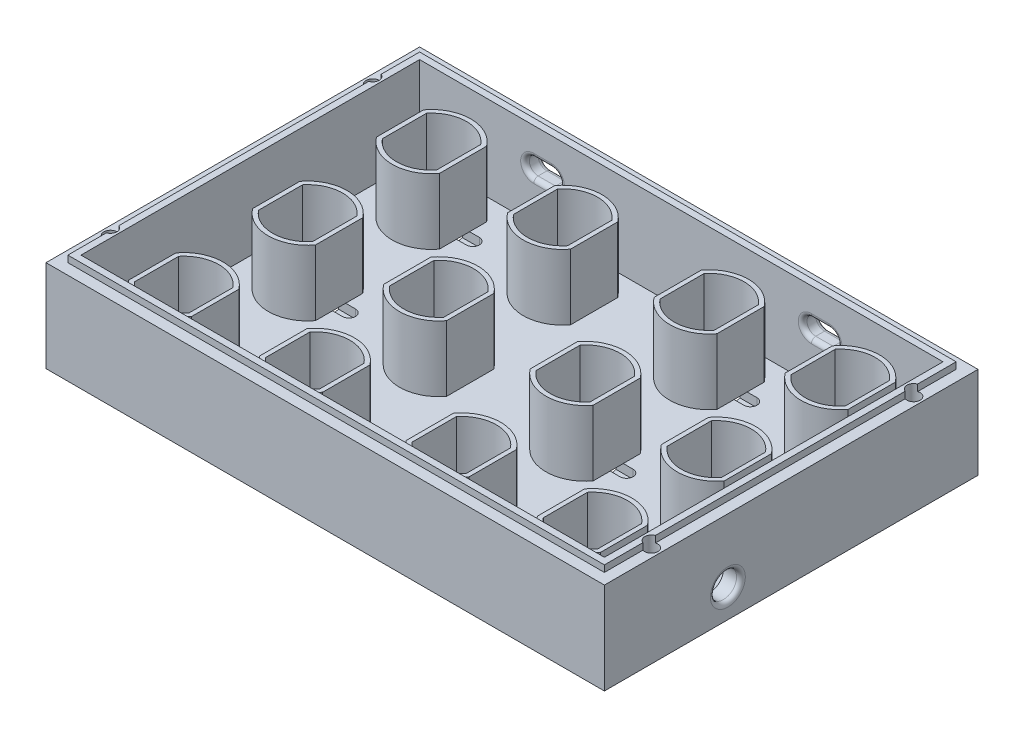
SolidWorks part; units mm, degrees
ref_plane "Front Plane" through (0, 0, 0) normal (0, 0, 1) x (1, 0, 0)
ref_plane "Top Plane" through (0, 0, 0) normal (0, 1, 0) x (1, 0, 0)
ref_plane "Right Plane" through (0, 0, 0) normal (1, 0, 0) x (0, 0, -1)
sketch "Sketch1" plane through (0, 0, 0) normal (0, 1, 0) x (1, 0, 0)
  line L0 (11.122, -9.411) -> (11.122, -19.379)
  line L1 (0, 0) -> (127.76, 0)
  line L2 (0, 0) -> (0, -85.48)
  line L3 (0, -85.48) -> (127.76, -85.48)
  line L4 (127.76, 0) -> (127.76, -85.48)
  line L5 (23.122, -9.411) -> (23.122, -19.379)
  line L6 (41.122, -9.411) -> (41.122, -19.379)
  line L7 (53.122, -9.411) -> (53.122, -19.379)
  line L8 (74.638, -9.411) -> (74.638, -19.379)
  line L9 (86.638, -9.411) -> (86.638, -19.379)
  line L10 (104.638, -9.411) -> (104.638, -19.379)
  line L11 (116.638, -9.411) -> (116.638, -19.379)
  line L12 (41.122, -37.756) -> (41.122, -47.724)
  line L13 (53.122, -37.756) -> (53.122, -47.724)
  line L14 (74.638, -37.756) -> (74.638, -47.724)
  line L15 (86.638, -37.756) -> (86.638, -47.724)
  line L16 (104.638, -37.756) -> (104.638, -47.724)
  line L17 (116.638, -37.756) -> (116.638, -47.724)
  line L18 (41.122, -66.101) -> (41.122, -76.069)
  line L19 (53.122, -66.101) -> (53.122, -76.069)
  line L20 (74.638, -66.101) -> (74.638, -76.069)
  line L21 (86.638, -66.101) -> (86.638, -76.069)
  line L22 (104.638, -66.101) -> (104.638, -76.069)
  line L23 (116.638, -66.101) -> (116.638, -76.069)
  line L24 (11.122, -37.756) -> (11.122, -47.724)
  line L25 (23.122, -37.756) -> (23.122, -47.724)
  line L26 (11.122, -66.101) -> (11.122, -76.069)
  line L27 (23.122, -66.101) -> (23.122, -76.069)
  circle A2 centre (17.122, -14.395) radius 14.05
  circle A12 centre (47.122, -14.395) radius 14.05
  circle A13 centre (80.638, -14.395) radius 14.05
  circle A14 centre (110.638, -14.395) radius 14.05
  circle A15 centre (47.122, -42.74) radius 14.05
  circle A16 centre (80.638, -42.74) radius 14.05
  circle A17 centre (110.638, -42.74) radius 14.05
  circle A18 centre (47.122, -71.085) radius 14.05
  circle A19 centre (80.638, -71.085) radius 14.05
  circle A20 centre (110.638, -71.085) radius 14.05
  circle A21 centre (17.122, -42.74) radius 14.05
  circle A22 centre (17.122, -71.085) radius 14.05
  arc A23 (11.122, -19.379) -> (23.122, -19.379) centre (17.122, -14.395) ccw
  arc A24 (23.122, -9.411) -> (11.122, -9.411) centre (17.122, -14.395) ccw
  arc A25 (41.122, -19.379) -> (53.122, -19.379) centre (47.122, -14.395) ccw
  arc A26 (53.122, -9.411) -> (41.122, -9.411) centre (47.122, -14.395) ccw
  arc A27 (74.638, -19.379) -> (86.638, -19.379) centre (80.638, -14.395) ccw
  arc A28 (86.638, -9.411) -> (74.638, -9.411) centre (80.638, -14.395) ccw
  arc A29 (104.638, -19.379) -> (116.638, -19.379) centre (110.638, -14.395) ccw
  arc A30 (116.638, -9.411) -> (104.638, -9.411) centre (110.638, -14.395) ccw
  arc A31 (41.122, -47.724) -> (53.122, -47.724) centre (47.122, -42.74) ccw
  arc A32 (53.122, -37.756) -> (41.122, -37.756) centre (47.122, -42.74) ccw
  arc A33 (74.638, -47.724) -> (86.638, -47.724) centre (80.638, -42.74) ccw
  arc A34 (86.638, -37.756) -> (74.638, -37.756) centre (80.638, -42.74) ccw
  arc A35 (104.638, -47.724) -> (116.638, -47.724) centre (110.638, -42.74) ccw
  arc A36 (116.638, -37.756) -> (104.638, -37.756) centre (110.638, -42.74) ccw
  arc A37 (41.122, -76.069) -> (53.122, -76.069) centre (47.122, -71.085) ccw
  arc A38 (53.122, -66.101) -> (41.122, -66.101) centre (47.122, -71.085) ccw
  arc A39 (74.638, -76.069) -> (86.638, -76.069) centre (80.638, -71.085) ccw
  arc A40 (86.638, -66.101) -> (74.638, -66.101) centre (80.638, -71.085) ccw
  arc A41 (104.638, -76.069) -> (116.638, -76.069) centre (110.638, -71.085) ccw
  arc A42 (116.638, -66.101) -> (104.638, -66.101) centre (110.638, -71.085) ccw
  arc A43 (11.122, -47.724) -> (23.122, -47.724) centre (17.122, -42.74) ccw
  arc A44 (23.122, -37.756) -> (11.122, -37.756) centre (17.122, -42.74) ccw
  arc A45 (11.122, -76.069) -> (23.122, -76.069) centre (17.122, -71.085) ccw
  arc A46 (23.122, -66.101) -> (11.122, -66.101) centre (17.122, -71.085) ccw
  point P15 (0, 0)
  point P17 (0, 0)
  point P34 (0, 0)
  point P35 (0, 0)
  point P44 (0, 0)
  point P49 (110.638, -42.9744)
  point P59 (82.4997, -14.7349)
  point P64 (110.638, -70.4806)
  point P69 (82.4997, -70.3296)
  point P74 (82.0649, -42.74)
  point P79 (17.122, -70.6281)
  point P89 (23.122, -19.379)
  point P91 (0, 0)
  point P92 (0, 0)
  point P93 (48.294, -44.3514)
  point P94 (0, 0)
  point P95 (0, 0)
  point P96 (46.1704, -70.4813)
  point P97 (0, 0)
  point P98 (110.638, -15.0922)
  point P99 (116.638, -19.379)
  point P100 (23.122, -76.069)
  point P101 (0, 0)
  point P102 (0, 0)
  point P103 (0, 0)
  point P104 (0, 0)
  point P105 (0, 0)
  point P106 (0, 0)
  point P107 (0, 0)
  dimension "D3" = 28.345
  dimension "D4" = 14.395
  dimension "D9" = 15.6
  dimension "D11" = 28.1
  dimension "D5" = 30
  dimension "D1" = 127.76
  dimension "D2" = 85.48
  dimension "D6" = 14.395
  dimension "D7" = 17.122
  dimension "D8" = 17.122
  dimension "D10" = 12
  dimension "D12" = 30
sketch "Sketch4" plane through (0, 0, 0) normal (0, 1, 0) x (1, 0, 0)
  line L44 (23.322, -19.4507) -> (23.322, -9.3393)
  line L45 (10.922, -9.3393) -> (10.922, -19.4507)
  line L46 (23.322, -19.4507) -> (23.322, -9.3393)
  line L47 (10.922, -9.3393) -> (10.922, -19.4507)
  line L50 (24.322, -19.795) -> (24.322, -8.995)
  line L51 (9.922, -8.995) -> (9.922, -19.795)
  line L52 (23.322, -47.7957) -> (23.322, -37.6843)
  line L53 (10.922, -37.6843) -> (10.922, -47.7957)
  line L54 (24.322, -48.14) -> (24.322, -37.34)
  line L55 (9.922, -37.34) -> (9.922, -48.14)
  line L56 (23.322, -76.1407) -> (23.322, -66.0293)
  line L57 (10.922, -66.0293) -> (10.922, -76.1407)
  line L58 (24.322, -76.485) -> (24.322, -65.685)
  line L59 (9.922, -65.685) -> (9.922, -76.485)
  line L60 (53.322, -19.4507) -> (53.322, -9.3393)
  line L61 (40.922, -9.3393) -> (40.922, -19.4507)
  line L62 (54.322, -19.795) -> (54.322, -8.995)
  line L63 (39.922, -8.995) -> (39.922, -19.795)
  line L64 (53.322, -47.7957) -> (53.322, -37.6843)
  line L65 (40.922, -37.6843) -> (40.922, -47.7957)
  line L66 (54.322, -48.14) -> (54.322, -37.34)
  line L67 (39.922, -37.34) -> (39.922, -48.14)
  line L68 (53.322, -76.1407) -> (53.322, -66.0293)
  line L69 (40.922, -66.0293) -> (40.922, -76.1407)
  line L70 (54.322, -76.485) -> (54.322, -65.685)
  line L71 (39.922, -65.685) -> (39.922, -76.485)
  line L72 (86.838, -19.4507) -> (86.838, -9.3393)
  line L73 (74.438, -9.3393) -> (74.438, -19.4507)
  line L74 (87.838, -19.795) -> (87.838, -8.995)
  line L75 (73.438, -8.995) -> (73.438, -19.795)
  line L76 (86.838, -47.7957) -> (86.838, -37.6843)
  line L77 (74.438, -37.6843) -> (74.438, -47.7957)
  line L78 (87.838, -48.14) -> (87.838, -37.34)
  line L79 (73.438, -37.34) -> (73.438, -48.14)
  line L80 (86.838, -76.1407) -> (86.838, -66.0293)
  line L81 (74.438, -66.0293) -> (74.438, -76.1407)
  line L82 (87.838, -76.485) -> (87.838, -65.685)
  line L83 (73.438, -65.685) -> (73.438, -76.485)
  line L84 (116.838, -19.4507) -> (116.838, -9.3393)
  line L85 (104.438, -9.3393) -> (104.438, -19.4507)
  line L86 (117.838, -19.795) -> (117.838, -8.995)
  line L87 (103.438, -8.995) -> (103.438, -19.795)
  line L88 (116.838, -47.7957) -> (116.838, -37.6843)
  line L89 (104.438, -37.6843) -> (104.438, -47.7957)
  line L90 (117.838, -48.14) -> (117.838, -37.34)
  line L91 (103.438, -37.34) -> (103.438, -48.14)
  line L92 (116.838, -76.1407) -> (116.838, -66.0293)
  line L93 (104.438, -66.0293) -> (104.438, -76.1407)
  line L94 (117.838, -76.485) -> (117.838, -65.685)
  line L95 (103.438, -65.685) -> (103.438, -76.485)
  arc A71 (24.322, -8.995) -> (9.922, -8.995) centre (17.122, -14.395) ccw
  arc A72 (9.922, -19.795) -> (24.322, -19.795) centre (17.122, -14.395) ccw
  arc A73 (24.322, -37.34) -> (9.922, -37.34) centre (17.122, -42.74) ccw
  arc A74 (9.922, -48.14) -> (24.322, -48.14) centre (17.122, -42.74) ccw
  arc A75 (10.922, -47.7957) -> (23.322, -47.7957) centre (17.122, -42.74) ccw
  arc A76 (23.322, -37.6843) -> (10.922, -37.6843) centre (17.122, -42.74) ccw
  arc A77 (24.322, -65.685) -> (9.922, -65.685) centre (17.122, -71.085) ccw
  arc A78 (9.922, -76.485) -> (24.322, -76.485) centre (17.122, -71.085) ccw
  arc A79 (10.922, -76.1407) -> (23.322, -76.1407) centre (17.122, -71.085) ccw
  arc A80 (23.322, -66.0293) -> (10.922, -66.0293) centre (17.122, -71.085) ccw
  arc A81 (54.322, -8.995) -> (39.922, -8.995) centre (47.122, -14.395) ccw
  arc A82 (39.922, -19.795) -> (54.322, -19.795) centre (47.122, -14.395) ccw
  arc A83 (54.322, -37.34) -> (39.922, -37.34) centre (47.122, -42.74) ccw
  arc A84 (39.922, -48.14) -> (54.322, -48.14) centre (47.122, -42.74) ccw
  arc A85 (40.922, -47.7957) -> (53.322, -47.7957) centre (47.122, -42.74) ccw
  arc A86 (53.322, -37.6843) -> (40.922, -37.6843) centre (47.122, -42.74) ccw
  arc A87 (54.322, -65.685) -> (39.922, -65.685) centre (47.122, -71.085) ccw
  arc A88 (39.922, -76.485) -> (54.322, -76.485) centre (47.122, -71.085) ccw
  arc A89 (40.922, -76.1407) -> (53.322, -76.1407) centre (47.122, -71.085) ccw
  arc A90 (53.322, -66.0293) -> (40.922, -66.0293) centre (47.122, -71.085) ccw
  arc A91 (40.922, -19.4507) -> (53.322, -19.4507) centre (47.122, -14.395) ccw
  arc A92 (53.322, -9.3393) -> (40.922, -9.3393) centre (47.122, -14.395) ccw
  arc A93 (87.838, -8.995) -> (73.438, -8.995) centre (80.638, -14.395) ccw
  arc A94 (73.438, -19.795) -> (87.838, -19.795) centre (80.638, -14.395) ccw
  arc A95 (87.838, -37.34) -> (73.438, -37.34) centre (80.638, -42.74) ccw
  arc A96 (73.438, -48.14) -> (87.838, -48.14) centre (80.638, -42.74) ccw
  arc A97 (74.438, -47.7957) -> (86.838, -47.7957) centre (80.638, -42.74) ccw
  arc A98 (86.838, -37.6843) -> (74.438, -37.6843) centre (80.638, -42.74) ccw
  arc A99 (87.838, -65.685) -> (73.438, -65.685) centre (80.638, -71.085) ccw
  arc A100 (73.438, -76.485) -> (87.838, -76.485) centre (80.638, -71.085) ccw
  arc A101 (74.438, -76.1407) -> (86.838, -76.1407) centre (80.638, -71.085) ccw
  arc A102 (86.838, -66.0293) -> (74.438, -66.0293) centre (80.638, -71.085) ccw
  arc A103 (117.838, -8.995) -> (103.438, -8.995) centre (110.638, -14.395) ccw
  arc A104 (103.438, -19.795) -> (117.838, -19.795) centre (110.638, -14.395) ccw
  arc A105 (117.838, -37.34) -> (103.438, -37.34) centre (110.638, -42.74) ccw
  arc A106 (103.438, -48.14) -> (117.838, -48.14) centre (110.638, -42.74) ccw
  arc A107 (104.438, -47.7957) -> (116.838, -47.7957) centre (110.638, -42.74) ccw
  arc A108 (116.838, -37.6843) -> (104.438, -37.6843) centre (110.638, -42.74) ccw
  arc A109 (117.838, -65.685) -> (103.438, -65.685) centre (110.638, -71.085) ccw
  arc A110 (103.438, -76.485) -> (117.838, -76.485) centre (110.638, -71.085) ccw
  arc A111 (104.438, -76.1407) -> (116.838, -76.1407) centre (110.638, -71.085) ccw
  arc A112 (10.922, -19.4507) -> (23.322, -19.4507) centre (17.122, -14.395) ccw
  arc A113 (23.322, -9.3393) -> (10.922, -9.3393) centre (17.122, -14.395) ccw
  arc A114 (10.922, -19.4507) -> (23.322, -19.4507) centre (17.122, -14.395) ccw
  arc A115 (23.322, -9.3393) -> (10.922, -9.3393) centre (17.122, -14.395) ccw
  arc A116 (116.838, -66.0293) -> (104.438, -66.0293) centre (110.638, -71.085) ccw
  arc A117 (104.438, -19.4507) -> (116.838, -19.4507) centre (110.638, -14.395) ccw
  arc A118 (116.838, -9.3393) -> (104.438, -9.3393) centre (110.638, -14.395) ccw
  arc A119 (74.438, -19.4507) -> (86.838, -19.4507) centre (80.638, -14.395) ccw
  arc A120 (86.838, -9.3393) -> (74.438, -9.3393) centre (80.638, -14.395) ccw
  point P10 (0, 0)
  dimension "D3" = 2
  dimension "D4" = 3
  dimension "D1" = 0.2
  dimension "D2" = 1
  dimension "D5" = 2
extrude "Boss-Extrude1" add sketch "Sketch4" along normal blind 15 contours L62 A81 L63 A82 | L60 A92 L61 A91 | L50 A71 L51 A72 | L46 A115 L47 A114 | L54 A73 L55 A74 | L52 A76 L53 A75 | L58 A77 L59 A78 | L56 A80 L57 A79 | L70 A87 L71 A88 | L68 A90 L69 A89 | L82 A99 L83 A100 | L80 A102 L81 A101 | L92 A116 L93 A111 | L94 A109 L95 A110 | L90 A105 L91 A106 | L88 A108 L89 A107 | L76 A98 L77 A97 | L78 A95 L79 A96 | L66 A83 L67 A84 | L64 A86 L65 A85 | L74 A93 L75 A94 | L72 A120 L73 A119 | L86 A103 L87 A104 | L84 A118 L85 A117
sketch "Sketch5" plane through (0, 0, 0) normal (0, 1, 0) x (1, 0, 0)
  line L0 (4, -4) -> (4, -81.48)
  line L1 (0, 0) -> (127.76, 0)
  line L2 (0, 0) -> (0, -85.48)
  line L3 (0, -85.48) -> (127.76, -85.48)
  line L4 (127.76, 0) -> (127.76, -85.48)
  line L5 (4, -81.48) -> (123.76, -81.48)
  line L6 (123.76, -4) -> (123.76, -81.48)
  line L7 (4, -4) -> (123.76, -4)
  dimension "D1" = 4
extrude "Boss-Extrude2" add sketch "Sketch5" along normal blind 18 separate body
sketch "Sketch6" plane through (0, 0, 0) normal (0, -1, 0) x (1, 0, 0)
  line L1 (0, 85.48) -> (127.76, 85.48)
  line L2 (0, 85.48) -> (0, 0)
  line L3 (0, 0) -> (127.76, 0)
  line L4 (127.76, 85.48) -> (127.76, 0)
  circle A0 centre (17.122, 71.085) radius 5.75
  circle A12 centre (17.122, 42.74) radius 5.75
  circle A13 centre (17.122, 14.395) radius 5.75
  circle A14 centre (47.122, 42.74) radius 5.75
  circle A15 centre (47.122, 14.395) radius 5.75
  circle A16 centre (47.122, 71.085) radius 5.75
  circle A17 centre (80.638, 71.085) radius 5.75
  circle A18 centre (110.638, 71.085) radius 5.75
  circle A19 centre (110.638, 42.74) radius 5.75
  circle A20 centre (80.638, 42.74) radius 5.75
  circle A21 centre (80.638, 14.395) radius 5.75
  circle A22 centre (110.638, 14.395) radius 5.75
  point P9 (80.638, 71.085)
  dimension "D3" = 11.5
  dimension "D1" = 3
  dimension "D2" = 2
extrude "Boss-Extrude3" add sketch "Sketch6" along normal blind 3
sketch "Sketch8" plane through (0, 0, 0) normal (0, 1, 0) x (1, 0, 0)
  line L0 (127.76, 0) -> (0, 0) construction
  line L1 (2.572, 0) -> (31.672, 0)
  line L2 (2.572, 0) -> (2.572, -85.48)
  line L3 (2.572, -85.48) -> (31.672, -85.48)
  line L4 (31.672, 0) -> (31.672, -85.48)
  line L5 (0, -85.48) -> (127.76, -85.48) construction
  line L6 (0, -85.48) -> (127.76, -85.48) construction
  line L7 (61.672, -85.48) -> (32.572, -85.48)
  line L8 (61.672, -85.48) -> (61.672, 0)
  line L9 (61.672, 0) -> (32.572, 0)
  line L10 (32.572, -85.48) -> (32.572, 0)
  line L11 (0, 0) -> (127.76, 0) construction
  point P8 (17.122, -85.48)
  point P19 (47.122, -85.48)
  dimension "D1" = 29.1
  dimension "D2" = 29.1
sketch "Sketch10" plane through (0, 18, 0) normal (0, 1, 0) x (1, 0, 0)
  line L9 (4, -4) -> (123.76, -4)
  line L10 (4, -4) -> (4, -81.48)
  line L11 (4, -81.48) -> (123.76, -81.48)
  line L12 (125.26, -82.98) -> (125.26, -2.5)
  line L13 (2.5, -82.98) -> (125.26, -82.98)
  line L14 (2.5, -2.5) -> (2.5, -82.98)
  line L15 (125.26, -2.5) -> (2.5, -2.5)
  line L16 (125.26, -82.98) -> (125.26, -2.5)
  line L17 (2.5, -82.98) -> (125.26, -82.98)
  line L18 (2.5, -2.5) -> (2.5, -82.98)
  line L19 (125.26, -2.5) -> (2.5, -2.5)
  line L20 (123.76, -4) -> (123.76, -81.48)
  dimension "D1" = 1.5
extrude "Boss-Extrude4" add sketch "Sketch10" along normal blind 1.5
sketch "Sketch11" plane through (0, 19.5, 0) normal (0, 1, 0) x (1, 0, 0)
  line L3 (127.76, 0) -> (0, 0) construction
  line L4 (0, 0) -> (0, -85.48) construction
  line L5 (127.76, -85.48) -> (127.76, 0) construction
  circle A0 centre (2, -12.74) radius 1.5
  circle A1 centre (2, -72.74) radius 1.5
  circle A2 centre (125.76, -12.74) radius 1.5
  circle A3 centre (125.76, -72.74) radius 1.5
  dimension "D1" = 3
  dimension "D3" = 12.74
  dimension "D4" = 2
  dimension "D2" = 60
  dimension "D5" = 2
extrude "Cut-Extrude1" cut sketch "Sketch11" against normal blind 4.5
sketch "Sketch13" plane through (0, 0, 0) normal (0, 1, 0) x (1, 0, 0)
  line L0 (17.122, -14.395) -> (26.572, -14.395) construction
  line L3 (17.122, -12.895) -> (26.572, -12.895)
  line L4 (17.122, -15.895) -> (26.572, -15.895)
  line L7 (24.322, -19.795) -> (24.322, -8.995) construction
  line L10 (37.672, -14.395) -> (47.122, -14.395) construction
  line L13 (37.672, -12.895) -> (47.122, -12.895)
  line L16 (37.672, -15.895) -> (47.122, -15.895)
  line L19 (37.672, -42.74) -> (47.122, -42.74) construction
  line L20 (37.672, -41.24) -> (47.122, -41.24)
  line L21 (37.672, -44.24) -> (47.122, -44.24)
  line L22 (37.672, -71.085) -> (47.122, -71.085) construction
  line L23 (37.672, -69.585) -> (47.122, -69.585)
  line L26 (37.672, -72.585) -> (47.122, -72.585)
  line L29 (17.122, -42.74) -> (26.572, -42.74) construction
  line L32 (17.122, -41.24) -> (26.572, -41.24)
  line L35 (17.122, -44.24) -> (26.572, -44.24)
  line L38 (17.122, -71.085) -> (26.572, -71.085) construction
  line L42 (17.122, -69.585) -> (26.572, -69.585)
  line L43 (17.122, -72.585) -> (26.572, -72.585)
  line L44 (80.638, -14.395) -> (90.088, -14.395) construction
  line L45 (80.638, -12.895) -> (90.088, -12.895)
  line L46 (80.638, -15.895) -> (90.088, -15.895)
  line L47 (101.188, -14.395) -> (110.638, -14.395) construction
  line L48 (101.188, -12.895) -> (110.638, -12.895)
  line L49 (101.188, -15.895) -> (110.638, -15.895)
  line L50 (101.188, -42.74) -> (110.638, -42.74) construction
  line L51 (101.188, -41.24) -> (110.638, -41.24)
  line L52 (101.188, -44.24) -> (110.638, -44.24)
  line L53 (101.188, -71.085) -> (110.638, -71.085) construction
  line L54 (101.188, -69.585) -> (110.638, -69.585)
  line L55 (101.188, -72.585) -> (110.638, -72.585)
  line L56 (80.638, -42.74) -> (90.088, -42.74) construction
  line L57 (80.638, -41.24) -> (90.088, -41.24)
  line L58 (80.638, -44.24) -> (90.088, -44.24)
  line L59 (80.638, -71.085) -> (90.088, -71.085) construction
  line L60 (80.638, -69.585) -> (90.088, -69.585)
  line L61 (80.638, -72.585) -> (90.088, -72.585)
  arc A12 (17.122, -12.895) -> (17.122, -15.895) centre (17.122, -14.395) ccw
  arc A13 (26.572, -15.895) -> (26.572, -12.895) centre (26.572, -14.395) ccw
  arc A14 (37.672, -12.895) -> (37.672, -15.895) centre (37.672, -14.395) ccw
  arc A15 (47.122, -15.895) -> (47.122, -12.895) centre (47.122, -14.395) ccw
  arc A30 (37.672, -41.24) -> (37.672, -44.24) centre (37.672, -42.74) ccw
  arc A31 (47.122, -44.24) -> (47.122, -41.24) centre (47.122, -42.74) ccw
  arc A32 (37.672, -69.585) -> (37.672, -72.585) centre (37.672, -71.085) ccw
  arc A33 (47.122, -72.585) -> (47.122, -69.585) centre (47.122, -71.085) ccw
  arc A34 (17.122, -41.24) -> (17.122, -44.24) centre (17.122, -42.74) ccw
  arc A35 (26.572, -44.24) -> (26.572, -41.24) centre (26.572, -42.74) ccw
  arc A36 (17.122, -69.585) -> (17.122, -72.585) centre (17.122, -71.085) ccw
  arc A37 (26.572, -72.585) -> (26.572, -69.585) centre (26.572, -71.085) ccw
  arc A38 (80.638, -12.895) -> (80.638, -15.895) centre (80.638, -14.395) ccw
  arc A39 (90.088, -15.895) -> (90.088, -12.895) centre (90.088, -14.395) ccw
  arc A40 (101.188, -12.895) -> (101.188, -15.895) centre (101.188, -14.395) ccw
  arc A41 (110.638, -15.895) -> (110.638, -12.895) centre (110.638, -14.395) ccw
  arc A42 (101.188, -41.24) -> (101.188, -44.24) centre (101.188, -42.74) ccw
  arc A43 (110.638, -44.24) -> (110.638, -41.24) centre (110.638, -42.74) ccw
  arc A44 (101.188, -69.585) -> (101.188, -72.585) centre (101.188, -71.085) ccw
  arc A45 (110.638, -72.585) -> (110.638, -69.585) centre (110.638, -71.085) ccw
  arc A46 (80.638, -41.24) -> (80.638, -44.24) centre (80.638, -42.74) ccw
  arc A47 (90.088, -44.24) -> (90.088, -41.24) centre (90.088, -42.74) ccw
  arc A48 (80.638, -69.585) -> (80.638, -72.585) centre (80.638, -71.085) ccw
  arc A49 (90.088, -72.585) -> (90.088, -69.585) centre (90.088, -71.085) ccw
  point P3 (21.847, -14.395)
  point P10 (110.638, -71.085)
  point P15 (42.397, -14.395)
  point P22 (42.397, -42.74)
  point P29 (42.397, -71.085)
  point P36 (21.847, -42.74)
  point P43 (21.847, -71.085)
  point P49 (85.363, -14.395)
  point P56 (105.913, -14.395)
  point P63 (105.913, -42.74)
  point P70 (105.913, -71.085)
  point P77 (85.363, -42.74)
  point P84 (85.363, -71.085)
  dimension "D1" = 1.5
  dimension "D4" = 3
  dimension "D2" = 2.25
  dimension "D3" = 2
  dimension "D5" = 2
extrude "Cut-Extrude3" cut sketch "Sketch13" against normal blind 5 from offset 3
sketch "Sketch14" plane through (0, 0, 0) normal (0, 0, -1) x (-1, 0, 0)
  line L0 (-97.638, 11) -> (-93.638, 11) construction
  line L1 (-97.638, 13) -> (-93.638, 13)
  line L2 (-97.638, 9) -> (-93.638, 9)
  line L3 (-34.122, 11) -> (-30.122, 11) construction
  line L4 (-34.122, 13) -> (-30.122, 13)
  line L5 (-34.122, 9) -> (-30.122, 9)
  line L6 (-103.438, 15) -> (-103.438, 0) construction
  line L7 (0, -3) -> (-127.76, -3) construction
  line L9 (-24.322, 15) -> (-24.322, 0) construction
  arc A0 (-97.638, 13) -> (-97.638, 9) centre (-97.638, 11) ccw
  arc A1 (-93.638, 9) -> (-93.638, 13) centre (-93.638, 11) ccw
  arc A2 (-34.122, 13) -> (-34.122, 9) centre (-34.122, 11) ccw
  arc A3 (-30.122, 9) -> (-30.122, 13) centre (-30.122, 11) ccw
  point P2 (-95.638, 11)
  point P11 (-32.122, 11)
  dimension "D3" = 2
  dimension "D6" = 5.8
  dimension "D2" = 4
  dimension "D4" = 12
  dimension "D5" = 5.8
  dimension "D1" = 2
extrude "Cut-Extrude4" cut sketch "Sketch14" against normal blind 5
fillet "Fillet1" radius 1 16 edges at (36.122, 11, 4) (32.122, 9, 4) (28.122, 11, 4) (99.638, 11, 4) (95.638, 9, 4) (91.638, 11, 4) (28.122, 11, 0) (32.122, 9, 0) (36.122, 11, 0) (91.638, 11, 0) (95.638, 9, 0) (99.638, 11, 0) (32.122, 13, 4) (95.638, 13, 4) (32.122, 13, 0) (95.638, 13, 0)
sketch "Sketch15" plane through (127.76, 0, 0) normal (1, 0, 0) x (0, 0, -1)
  line L0 (-81.48, 0) -> (-4, 0) construction
  line L1 (-62.085, 0) -> (-62.085, 15) construction
  circle A0 centre (-57.235, 3.5) radius 3
  dimension "D1" = 6
  dimension "D2" = 3.5
  dimension "D3" = 4.85
extrude "Cut-Extrude5" cut sketch "Sketch15" against normal blind 5
fillet "Fillet2" radius 1 1 edges at (127.76, 3.5, 54.235)
